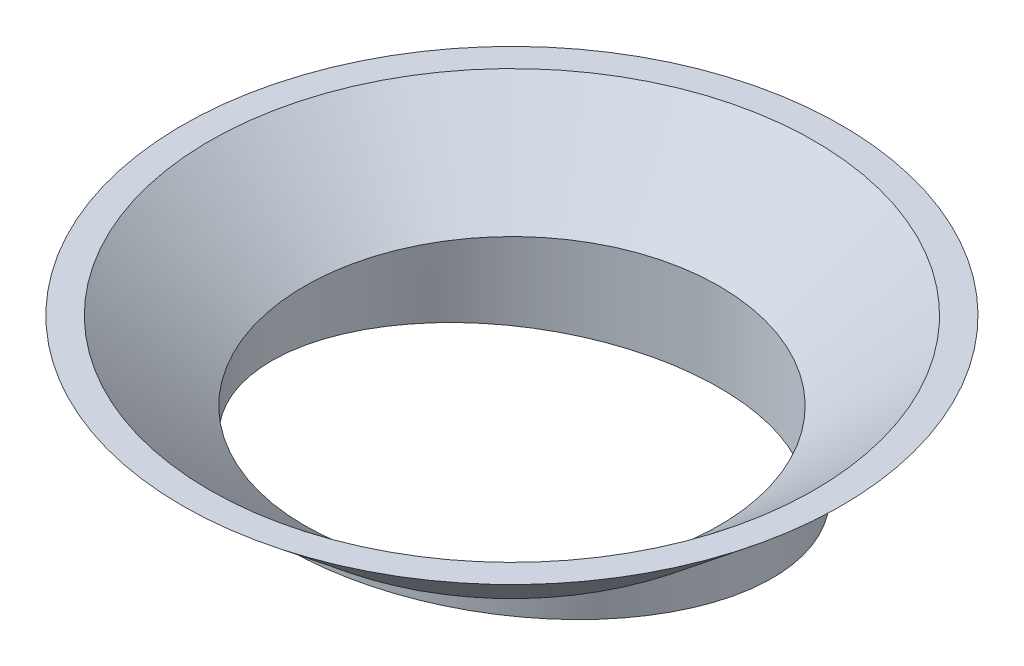
SolidWorks part; units mm, degrees
ref_plane "Front Plane" through (0, 0, 0) normal (0, 0, 1) x (1, 0, 0)
ref_plane "Top Plane" through (0, 0, 0) normal (0, 1, 0) x (1, 0, 0)
ref_plane "Right Plane" through (0, 0, 0) normal (1, 0, 0) x (0, 0, -1)
ref_axis "Axe1" through (0, 21, 0) along (0, -1, 0)
sketch "Esquisse1" plane through (0, 0, 0) normal (0, 0, 1) x (1, 0, 0)
  line L0 (26, 0) -> (26, 10)
  line L1 (26, 10) -> (38.1467, 20)
  line L2 (38.1467, 20) -> (35, 20)
  line L3 (35, 20) -> (24, 10.944)
  line L4 (24, 10.944) -> (24, 0)
  line L5 (24, 0) -> (26, 0)
  dimension "D1" = 2
  dimension "D2" = 35
  dimension "D3" = 24
  dimension "D4" = 10
  dimension "D5" = 20
  dimension "D6" = 2
revolve "Révolution1" add sketch "Esquisse1" angle 360 about axis through (0, 21, 0) along (0, -1, 0)
ref_plane "Plan3" through (0, 5, 0) normal (0, 1, 0) x (1, 0, 0)
ref_axis "Axe3" through (41.9614, 5, 0) along (-1, 0, 0)
ref_plane "Plan4" through (0, 4.8492, -0.8551) normal (0, 0.9848, -0.1736) x (-1, 0, 0)
sketch "Esquisse2" plane through (0, 4.8492, -0.8551) normal (0, 0.9848, -0.1736) x (-1, 0, 0)
  circle A0 centre (0, 0) radius 27.3415
  ellipse E0 centre (0, 1.7365) end of major axis (26, 1.7365) minor radius 25.605 construction
  point P2 (0, 0)
extrude "Enlèv. mat.-Extru.1" cut sketch "Esquisse2" against normal through all
